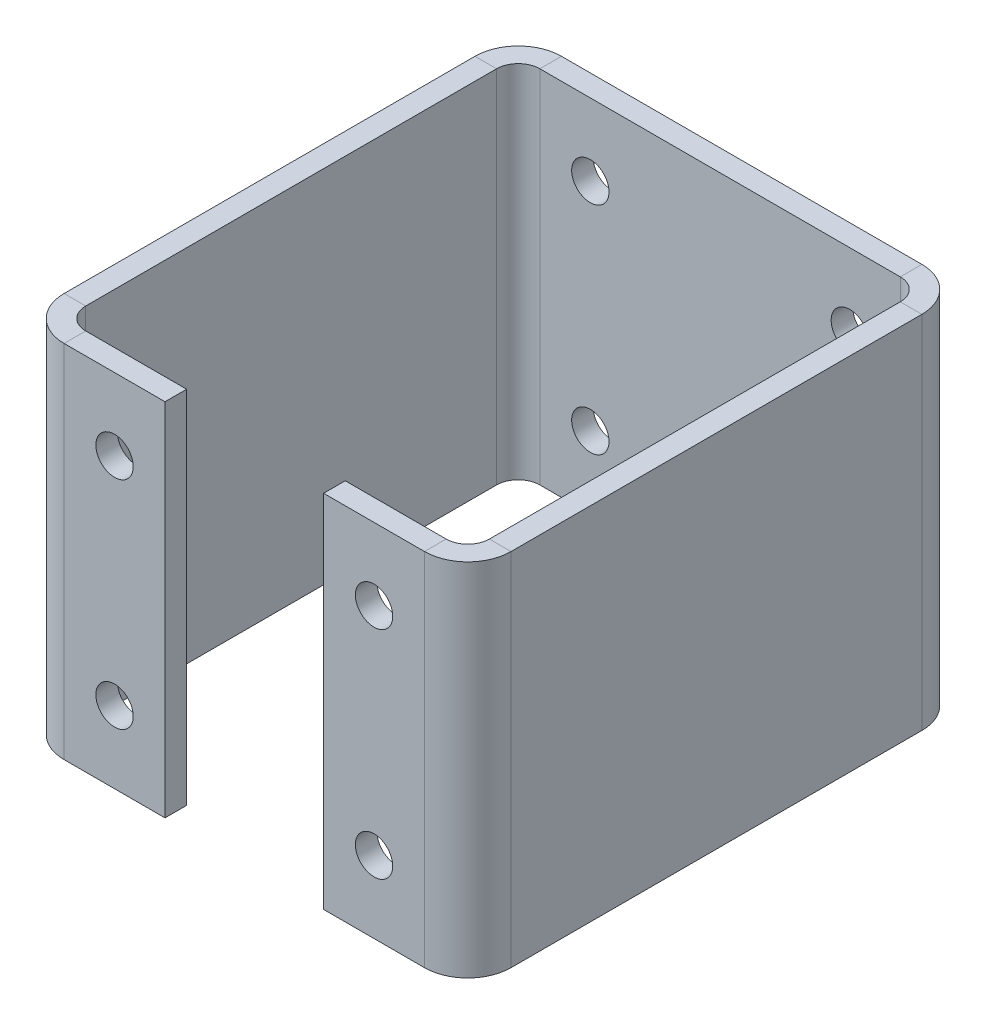
SolidWorks part; units mm, degrees
note: The reader was unsure of these and kept them because the rebuilt part matched: flange length of "Edge-Flange1", "Edge-Flange2", "Edge-Flange3", "Edge-Flange4".
ref_plane "Front Plane" through (0, 0, 0) normal (0, 0, 1) x (1, 0, 0)
ref_plane "Top Plane" through (0, 0, 0) normal (0, 1, 0) x (1, 0, 0)
ref_plane "Right Plane" through (0, 0, 0) normal (1, 0, 0) x (0, 0, -1)
sketch "Sketch1" plane through (0, 0, 0) normal (0, 0, 1) x (1, 0, 0)
  line L0 (25, 25) -> (-25, -25) construction
  line L1 (-25, 25) -> (25, 25)
  line L2 (-25, 25) -> (-25, -25)
  line L3 (-25, -25) -> (25, -25)
  line L4 (25, 25) -> (25, -25)
  point P4 (0, 0)
  dimension "D1" = 50
  dimension "D2" = 50
base flange "Base-Flange1" sketch "Sketch1" thickness 3 reverse thickness direction no parameters "D1"=3
edge flange "Edge-Flange1" sketch "Sketch8" flange angle 90 flange length 60 flange position bend outside bend radius 3 thickness 3 parameters "D6"=10
sketch "Sketch8" plane through (25, 0, 0) normal (1, 0, 0) x (0, 1, 0)
  line L2 (-25, 0) -> (-25, 60)
  line L3 (-25, 60) -> (25, 60)
  line L4 (25, 60) -> (25, 0)
  line L5 (-25, 0) -> (25, 0) construction
  line L6 (-25, 0) -> (25, 0)
bend "EdgeBend1" bend radius 3 bend angle 90 parameters "D5"=1
edge flange "Edge-Flange2" sketch "Sketch11" flange angle 90 flange length 60 flange position bend outside bend radius 3 thickness 3 parameters "D6"=10
sketch "Sketch11" plane through (-25, 0, 0) normal (-1, 0, 0) x (0, -1, 0)
  line L0 (-25, 0) -> (25, 0) construction
  line L1 (-25, 0) -> (25, 0)
  line L2 (-25, 0) -> (-25, 60)
  line L3 (-25, 60) -> (25, 60)
  line L4 (25, 60) -> (25, 0)
bend "EdgeBend2" bend radius 3 bend angle 90 parameters "D5"=2
edge flange "Edge-Flange3" sketch "Sketch14" flange angle 90 flange length 20 flange position bend outside bend radius 3 thickness 3 parameters "D6"=10
sketch "Sketch14" plane through (-28, 0, 60) normal (0, 0, 1) x (0, -1, 0)
  line L0 (25, 0) -> (-25, 0) construction
  line L1 (25, 0) -> (-25, 0)
  line L2 (-25, 0) -> (-25, 17)
  line L3 (-25, 17) -> (25, 17)
  line L4 (25, 17) -> (25, 0)
bend "EdgeBend3" bend radius 3 bend angle 90 parameters "D5"=3
edge flange "Edge-Flange4" sketch "Sketch19" flange angle 90 flange length 20 flange position bend outside bend radius 3 thickness 3 parameters "D6"=10
sketch "Sketch19" plane through (28, 0, 60) normal (0, 0, 1) x (0, 1, 0)
  line L0 (25, 0) -> (-25, 0) construction
  line L1 (25, 0) -> (-25, 0)
  line L2 (-25, 0) -> (-25, 17)
  line L3 (-25, 17) -> (25, 17)
  line L4 (25, 17) -> (25, 0)
bend "EdgeBend4" bend radius 3 bend angle 90 parameters "D5"=4
hole_wizard "#6 (0.204) Diameter Slot1" positions "Sketch21" profile "Sketch20" size "#6" standard "ANSI Inch" slot yes end condition through all
sketch "Sketch21" plane through (0, 0, 66) normal (0, 0, 1) x (1, 0, 0)
  line L0 (-11, 25) -> (-25, 25) construction
  line L1 (-25, -25) -> (-11, -25) construction
  line L2 (-11, -25) -> (-11, 25) construction
  line L3 (25, 25) -> (11, 25) construction
  line L4 (25, 25) -> (25, -25) construction
  line L5 (11, -25) -> (25, -25) construction
  point P0 (-18, 15)
  point P2 (-18, -15)
  point P4 (18, 15)
  point P6 (18, -15)
  dimension "D1" = 10
  dimension "D2" = 10
  dimension "D3" = 7
  dimension "D4" = 7
  dimension "D5" = 10
  dimension "D6" = 7
  dimension "D7" = 7
  dimension "D8" = 10
sketch "Sketch20" plane through (-18, 15, 66) normal (1, 0, 0) x (0, -1, 0)
  line L0 (0, 0) -> (0, 69)
  line L1 (0, 69) -> (2.5908, 69)
  line L2 (2.5908, 69) -> (2.5908, 0)
  line L5 (2.5908, 0) -> (0, 0)
  line L11 (0, -6.35) -> (0, 107.95) construction
  dimension "Thru Hole Dia." = 5.1816
  dimension "Thru Hole Depth" = 69
sketch "Bend-Lines1" plane through (0, 0, 0) normal (0, 1, 0) x (1, 0, 0)
sketch "Bounding-Box1" plane through (0, 0, 0) normal (0, 1, 0) x (1, 0, 0)
sheet metal parameters "Sheet-Metal1" thickness 3 parameters "D1"=3
flat pattern "Flat-Pattern1" [suppressed]
sketch "Bend-Lines2" plane through (0, 0, 0) normal (0, 1, 0) x (1, 0, 0)
sketch "Bounding-Box2" [suppressed] plane through (0, 0, 0) normal (0, 1, 0) x (1, 0, 0)
sheet metal parameters "Sheet-Metal2" thickness 3 parameters "D1"=3
flat pattern "Flat-Pattern1" [suppressed]
sketch "Bend-Lines2" plane through (0, 0, 0) normal (0, 1, 0) x (1, 0, 0)
sketch "Bounding-Box2" [suppressed] plane through (0, 0, 0) normal (0, 1, 0) x (1, 0, 0)
bend of the flat pattern "Flatten-<EdgeBend1>1"
sheet metal parameters "Sheet-Metal3" thickness 3 parameters "D1"=3
flat pattern "Flat-Pattern1" [suppressed]
sketch "Bend-Lines2" plane through (0, 0, 0) normal (0, 1, 0) x (1, 0, 0)
sketch "Bounding-Box2" [suppressed] plane through (0, 0, 0) normal (0, 1, 0) x (1, 0, 0)
bend of the flat pattern "Flatten-<EdgeBend1>1"
bend of the flat pattern "Flatten-<EdgeBend2>1"
sheet metal parameters "Sheet-Metal4" thickness 3 parameters "D1"=3
flat pattern "Flat-Pattern1" [suppressed]
sketch "Bend-Lines2" plane through (0, 0, 0) normal (0, 1, 0) x (1, 0, 0)
sketch "Bounding-Box2" [suppressed] plane through (0, 0, 0) normal (0, 1, 0) x (1, 0, 0)
bend of the flat pattern "Flatten-<EdgeBend1>1"
bend of the flat pattern "Flatten-<EdgeBend2>1"
bend of the flat pattern "Flatten-<EdgeBend3>1"
sheet metal parameters "Sheet-Metal5" thickness 3 parameters "D1"=3
flat pattern "Flat-Pattern1" [suppressed]
sketch "Bend-Lines2" plane through (0, 0, 0) normal (0, 1, 0) x (1, 0, 0)
sketch "Bounding-Box2" [suppressed] plane through (0, 0, 0) normal (0, 1, 0) x (1, 0, 0)
bend of the flat pattern "Flatten-<EdgeBend1>1"
bend of the flat pattern "Flatten-<EdgeBend2>1"
bend of the flat pattern "Flatten-<EdgeBend3>1"
bend of the flat pattern "Flatten-<EdgeBend4>1"
sheet metal parameters "Sheet-Metal6" thickness 3 parameters "D1"=3
flat pattern "Flat-Pattern1" [suppressed]
sketch "Bend-Lines2" plane through (0, 0, 0) normal (0, 1, 0) x (1, 0, 0)
sketch "Bounding-Box2" [suppressed] plane through (0, 0, 0) normal (0, 1, 0) x (1, 0, 0)
bend of the flat pattern "Flatten-<EdgeBend1>1"
bend of the flat pattern "Flatten-<EdgeBend2>1"
bend of the flat pattern "Flatten-<EdgeBend3>1"
bend of the flat pattern "Flatten-<EdgeBend4>1"
